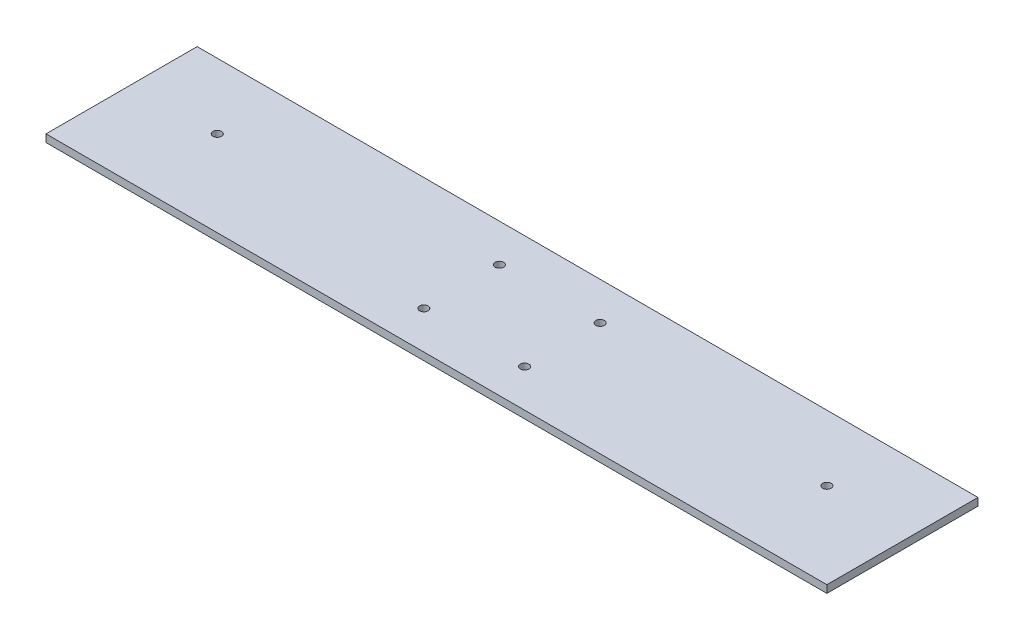
SolidWorks part; units mm, degrees
material "3.0526 (EN-AW 3005)"
ref_plane "Płaszczyzna przednia" through (0, 0, 0) normal (0, 0, 1) x (1, 0, 0)
ref_plane "Płaszczyzna górna" through (0, 0, 0) normal (0, 1, 0) x (1, 0, 0)
ref_plane "Płaszczyzna prawa" through (0, 0, 0) normal (1, 0, 0) x (0, 0, -1)
sketch "Sketch1" plane through (0, 0, 0) normal (0, 1, 0) x (1, 0, 0)
  line L1 (-10, 0) -> (300, 0)
  line L2 (-10, 0) -> (-10, 60)
  line L3 (-10, 60) -> (300, 60)
  line L4 (300, 0) -> (300, 60)
  dimension "D1" = 310
  dimension "D2" = 60
extrude "Boss-Extrude1" add sketch "Sketch1" along normal blind 3
hole_wizard "Otwór pod śrubę M31" positions "Sketch2" profile "Sketch3" hole size "M3" standard "Ansi Metric" end condition through all
sketch "Sketch2" plane through (0, 3, 0) normal (0, 1, 0) x (1, 0, 0)
  line L0 (-10, 60) -> (-10, 0) construction
  line L1 (-10, 0) -> (300, 0) construction
  line L2 (300, 0) -> (300, 60) construction
  line L3 (300, 60) -> (-10, 60) construction
  point P0 (266, 34)
  point P2 (24, 34)
  point P20 (125, 15)
  point P22 (165, 15)
  point P24 (165, 45)
  point P26 (125, 45)
  dimension "D1" = 34
  dimension "D2" = 34
  dimension "D3" = 34
  dimension "D4" = 34
  dimension "D11" = 15
  dimension "D12" = 15
  dimension "D15" = 15
  dimension "D16" = 15
  dimension "D25" = 40
  dimension "D26" = 40
  dimension "D27" = 135
  dimension "D28" = 135
sketch "Sketch3" plane through (266, 3, -34) normal (1, 0, 0) x (0, 0, 1)
  line L0 (0, 0) -> (0, 3)
  line L1 (0, 3) -> (1.7, 3)
  line L2 (1.7, 3) -> (1.7, 0)
  line L5 (1.7, 0) -> (0, 0)
  line L11 (0, -6.35) -> (0, 107.95) construction
  dimension "Œrednica otworu na wylot" = 3.4
  dimension "G³êbokoœæ otworu na wylot" = 3
